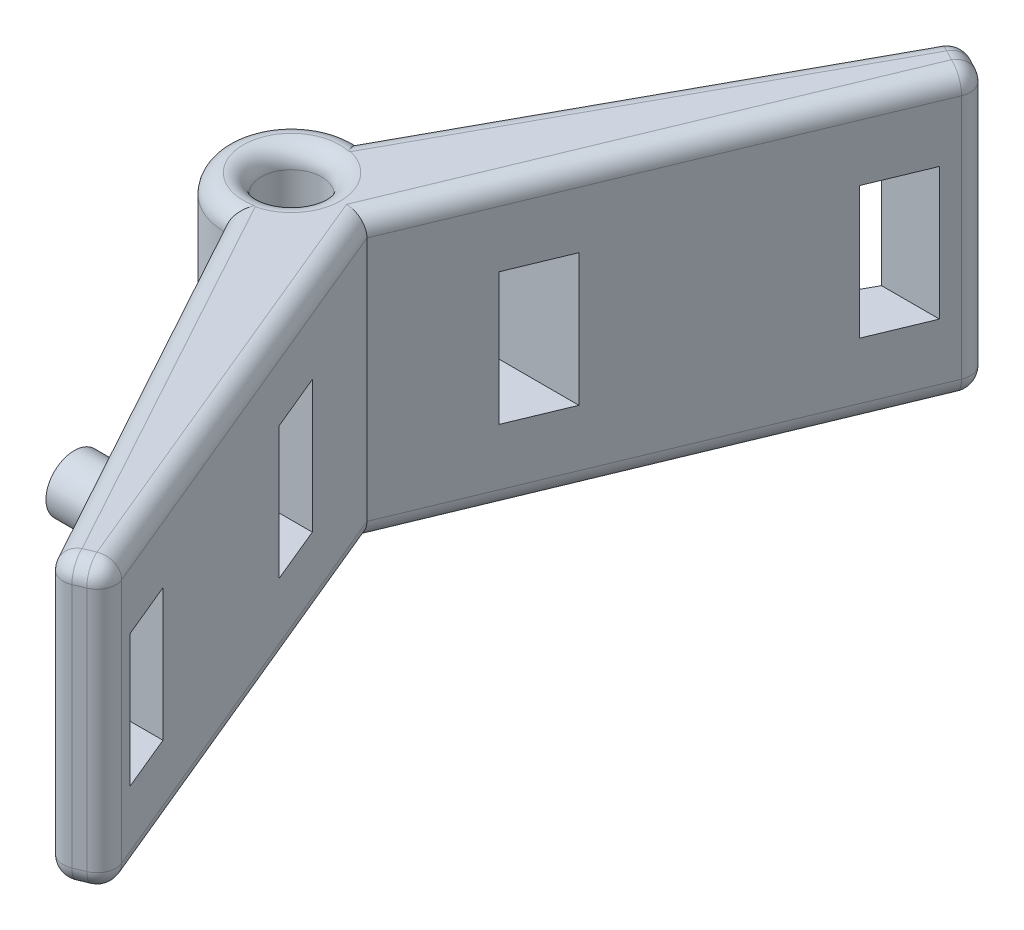
SolidWorks part; units mm, degrees
ref_plane "Спереди" through (0, 0, 0) normal (0, 0, 1) x (1, 0, 0)
ref_plane "Сверху" through (0, 0, 0) normal (0, 1, 0) x (1, 0, 0)
ref_plane "Справа" through (0, 0, 0) normal (1, 0, 0) x (0, 0, -1)
sketch "Эскиз1" plane through (0, 0, 0) normal (0, 1, 0) x (1, 0, 0)
  line L0 (-994.9275, 0) -> (49005.0725, 0) construction
  line L1 (-33.5675, 0) -> (-25, 20.6838) construction
  line L2 (-33.5675, 0) -> (-25, -20.6838) construction
  line L3 (-29.4124, 23.097) -> (-38.9795, 0)
  line L4 (-38.9795, 0) -> (-29.4124, -23.097)
  line L5 (-29.4124, 23.097) -> (-31.6058, 24.2966)
  line L6 (-31.6058, 24.2966) -> (-42.9795, 3.5)
  line L7 (-42.9795, -3.5) -> (-31.7221, -24.0537)
  line L8 (-31.7221, -24.0537) -> (-29.4124, -23.097)
  line L9 (-25, -979.3162) -> (-25, 49020.6838) construction
  arc A1 (-42.9795, 3.5) -> (-42.9795, -3.5) centre (-42.9795, 0) ccw
  circle A2 centre (-42.9795, 0) radius 1.6
  dimension "D6" = 7
  dimension "D10" = 3.2
  dimension "D2" = 67.5
  dimension "D3" = 67.5
  dimension "D4" = 5
  dimension "D5" = 25
  dimension "D7" = 4
  dimension "D8" = 2.5
  dimension "D9" = 2.5
  dimension "D11" = 25
extrude "Бобышка-Вытянуть1" add sketch "Эскиз1" along normal blind 15
ref_plane "Плоскость4" through (-42.9795, 0, 0) normal (1, 0, 0) x (0, 0, -1)
sketch "Эскиз2" plane through (-42.9795, 0, 0) normal (1, 0, 0) x (0, 0, -1)
  line L0 (0, -1000) -> (0, 49000) construction
  line L1 (-3.5, 0) -> (3.5, 0) construction
  line L2 (-1033.2925, 7.5) -> (48966.7075, 7.5) construction
  line L3 (-24.0537, 15) -> (-24.0537, 0) construction
  circle A0 centre (12.5, 7.5) radius 1.5
  circle A1 centre (-12.5, 7.5) radius 1.5
  point P9 (0, 0)
  point P14 (-24.0537, 7.5)
  dimension "D1" = 25
  dimension "D2" = 3
extrude "Бобышка-Вытянуть2" add sketch "Эскиз2" along normal blind 7 from offset 1
fillet "Скругление1" radius 1 20 edges at (-42.9795, 0, 1.6) (-37.2926, 0, -13.8983) (-46.4795, 0, 0) (-37.3508, 0, 13.7768) (-30.5673, 0, 23.5753) (-34.1959, 0, 11.5485) (-34.1959, 0, -11.5485) (-30.5091, 0, -23.6968) (-42.9795, 15, 1.6) (-34.1959, 15, -11.5485) (-34.1959, 15, 11.5485) (-30.5673, 15, 23.5753) (-37.3508, 15, 13.7768) (-46.4795, 15, 0) (-37.2926, 15, -13.8983) (-30.5091, 15, -23.6968) (-31.7221, 7.5, 24.0537) (-31.6058, 7.5, -24.2966) (-29.4124, 7.5, -23.097) (-29.4124, 7.5, 23.097)
sketch "Эскиз3" plane through (0, 0, 0) normal (1, 0, 0) x (0, 0, -1)
  line L0 (0, -999.9987) -> (0, 49000.0013) construction
  line L1 (21.4394, 11) -> (18.4394, 11)
  line L2 (21.4394, 11) -> (21.4394, 4)
  line L3 (21.4394, 4) -> (18.4394, 4)
  line L4 (18.4394, 11) -> (18.4394, 4)
  line L5 (7.9394, 11) -> (4.9394, 11)
  line L6 (7.9394, 11) -> (7.9394, 4)
  line L7 (7.9394, 4) -> (4.9394, 4)
  line L8 (4.9394, 11) -> (4.9394, 4)
  line L17 (-2.55, 0.0013) -> (2.55, 0.0013) construction
  line L18 (-976.5808, 7.5) -> (49023.4192, 7.5) construction
  line L19 (23.4192, 14) -> (23.4192, 1) construction
  line L20 (23.9394, 1) -> (23.9394, 14) construction
  line L21 (-4.9394, 11) -> (-4.9394, 4)
  line L22 (-7.9394, 4) -> (-4.9394, 4)
  line L23 (-7.9394, 11) -> (-7.9394, 4)
  line L24 (-7.9394, 11) -> (-4.9394, 11)
  line L25 (-18.4394, 11) -> (-18.4394, 4)
  line L26 (-21.4394, 4) -> (-18.4394, 4)
  line L27 (-21.4394, 11) -> (-21.4394, 4)
  line L28 (-21.4394, 11) -> (-18.4394, 11)
  point P13 (0, 0.0013)
  point P18 (23.4192, 7.5)
  dimension "D1" = 3
  dimension "D2" = 2.5
  dimension "D3" = 10.5
  dimension "D4" = 7
extrude "Вырез-Вытянуть1" cut sketch "Эскиз3" against normal blind 56
